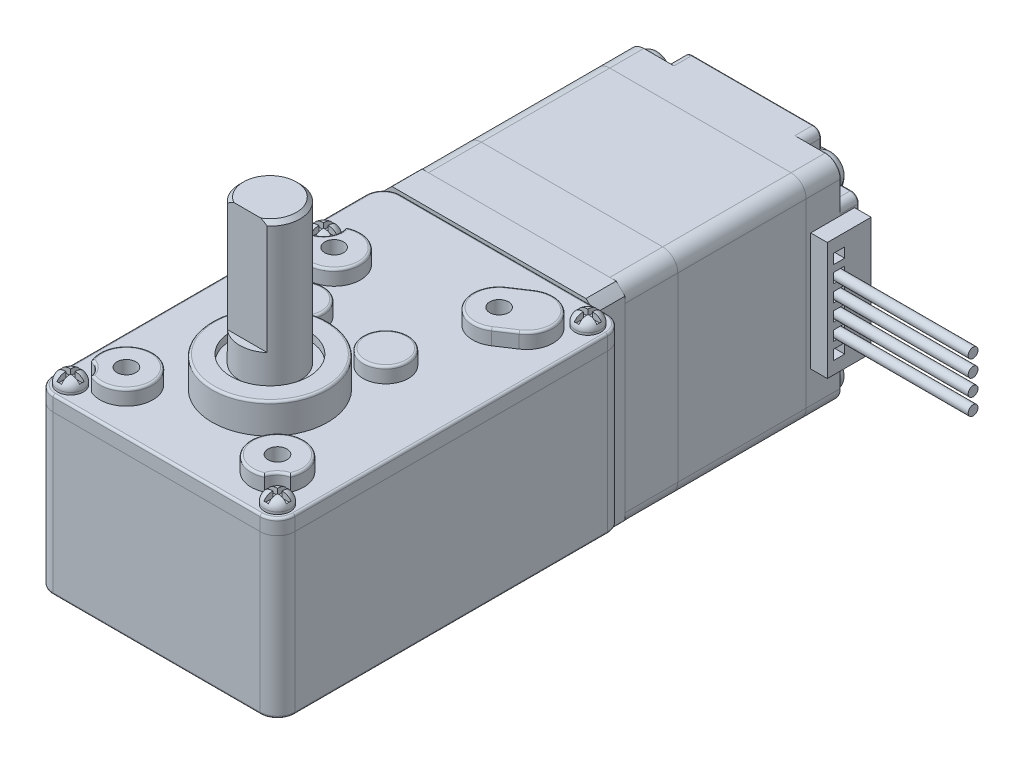
SolidWorks part; units mm, degrees
ref_plane "前视基准面" through (0, 0, 0) normal (0, 0, 1) x (1, 0, 0)
ref_plane "上视基准面" through (0, 0, 0) normal (0, 1, 0) x (1, 0, 0)
ref_plane "右视基准面" through (0, 0, 0) normal (1, 0, 0) x (0, 0, -1)
sketch "草图1" plane through (0, 0, 0) normal (0, 0, 1) x (1, 0, 0)
  line L0 (-49.7438, 0) -> (46.5346, 0) construction
  line L1 (0, 31.2288) -> (0, -36.9067) construction
  line L2 (-14, -14) -> (14, -14)
  line L3 (-14, 14) -> (-14, -14)
  line L4 (-14, 14) -> (14, 14)
  line L5 (14, 14) -> (14, -14)
  line L6 (-49.7438, -14) -> (46.5346, -14) construction
  line L7 (-14, 31.2288) -> (-14, -36.9067) construction
  line L8 (14, 31.2288) -> (14, -36.9067) construction
  line L9 (-49.7438, 14) -> (46.5346, 14) construction
  dimension "D1" = 14
  dimension "D2" = 14
extrude "拉伸1" add sketch "草图1" along normal blind 7
fillet "圆角5" radius 2 4 edges at (-14, -14, 3.5) (-14, 14, 3.5) (14, -14, 3.5) (14, 14, 3.5)
sketch "草图5" plane through (0, 0, 0) normal (0, 0, -1) x (-1, 0, 0)
  circle A0 centre (0, 0) radius 3
  dimension "D1" = 6
extrude "切除-拉伸1" cut sketch "草图5" against normal blind 2
sketch "草图6" plane through (0, 0, 0) normal (0, 0, -1) x (-1, 0, 0)
  line L0 (-24.7944, 0) -> (26.333, 0) construction
  line L1 (0, 25.3862) -> (0, -26.5696) construction
  line L2 (-11, 25.3862) -> (-11, -26.5696) construction
  line L3 (-24.7944, -11) -> (26.333, -11) construction
  line L4 (-14, -12) -> (-14, 12) construction
  line L5 (-14, -9) -> (-14, -14)
  line L6 (-9, -11) -> (-9, -14)
  line L7 (-14, -9) -> (-11, -9)
  line L8 (-14, -14) -> (-9, -14)
  line L9 (-9, 14) -> (-14, 14)
  line L10 (-9, 25.3862) -> (-9, -26.5696) construction
  line L11 (-14, 25.3862) -> (-14, -26.5696) construction
  line L12 (-24.7944, -9) -> (26.333, -9) construction
  line L13 (-24.7944, -14) -> (26.333, -14) construction
  line L14 (-11, 9) -> (-14, 9)
  line L15 (-9, 14) -> (-9, 11)
  line L16 (-14, 14) -> (-14, 9)
  line L17 (14, 9) -> (14, 14)
  line L18 (9, 11) -> (9, 14)
  line L19 (14, 9) -> (11, 9)
  line L20 (14, 14) -> (9, 14)
  line L21 (9, -14) -> (14, -14)
  line L22 (11, -9) -> (14, -9)
  line L23 (9, -14) -> (9, -11)
  line L24 (14, -14) -> (14, -9)
  arc A0 (-9, -11) -> (-11, -9) centre (-11, -11) ccw
  arc A1 (-11, 9) -> (-9, 11) centre (-11, 11) ccw
  arc A2 (9, 11) -> (11, 9) centre (11, 11) ccw
  arc A3 (11, -9) -> (9, -11) centre (11, -11) ccw
  point P21 (-9, 25.3862)
  point P22 (-9, -26.5696)
  point P23 (9, 25.3862)
  point P24 (9, -26.5696)
  point P25 (-24.7944, -9)
  point P26 (26.333, -9)
  point P27 (-24.7944, 9)
  point P28 (26.333, 9)
  point P29 (-14, 25.3862)
  point P30 (-14, -26.5696)
  point P31 (-24.7944, -14)
  point P32 (26.333, -14)
  point P33 (14, 25.3862)
  point P34 (14, -26.5696)
  point P35 (-24.7944, 14)
  point P36 (26.333, 14)
  dimension "D3" = 9
  dimension "D1" = 11
  dimension "D2" = 4
  dimension "D5" = 14
extrude "切除-拉伸2" cut sketch "草图6" against normal blind 2.5
sketch "草图40" plane through (0, 0, 7) normal (0, 0, 1) x (1, 0, 0)
  line L0 (-12, 14) -> (12, 14)
  line L1 (-12, -14) -> (12, -14) construction
  line L2 (14, 12) -> (14, -12)
  line L3 (12, 14) -> (-12, 14) construction
  line L4 (12, -14) -> (-12, -14)
  line L6 (-14, -12) -> (-14, 12)
  arc A0 (14, 12) -> (12, 14) centre (12, 12) ccw construction
  arc A1 (14, 12) -> (12, 14) centre (12, 12) ccw
  arc A2 (12, -14) -> (14, -12) centre (12, -12) ccw
  arc A3 (-14, -12) -> (-12, -14) centre (-12, -12) ccw
  arc A5 (-12, 14) -> (-14, 12) centre (-12, 12) ccw
extrude "凸台-拉伸28" add sketch "草图40" along normal blind 17 separate body
sketch "草图12" plane through (0, 0, 24) normal (0, 0, 1) x (1, 0, 0)
  line L0 (14, 12) -> (14, -12)
  line L1 (12, -14) -> (-12, -14)
  line L2 (-14, -12) -> (-14, 12)
  line L3 (-12, 14) -> (12, 14)
  arc A0 (-12, 14) -> (-14, 12) centre (-12, 12) ccw
  arc A1 (14, 12) -> (12, 14) centre (12, 12) ccw
  arc A2 (12, -14) -> (14, -12) centre (12, -12) ccw
  arc A3 (-14, -12) -> (-12, -14) centre (-12, -12) ccw
  arc A4 (14, 12) -> (12, 14) centre (12, 12) ccw construction
extrude "凸台-拉伸9" add sketch "草图12" along normal blind 7 separate body
sketch "草图14" plane through (0, 0, 31) normal (0, 0, -1) x (-1, 0, 0)
  line L0 (0, 14.44) -> (0, -16.3076) construction
  line L1 (14.7902, 0) -> (-17.5581, 0) construction
  line L4 (12.8452, 14) -> (-12.8452, 14)
  line L5 (-14, 12.8452) -> (-14, -12.8452)
  line L6 (12.8452, -14) -> (-12.8452, -14)
  line L7 (14, 12.8452) -> (14, -12.8452)
  line L9 (14.7902, 14) -> (-17.5581, 14) construction
  line L10 (-14, 14.44) -> (-14, -16.3076) construction
  line L11 (14.7902, -14) -> (-17.5581, -14) construction
  line L12 (14, 14.44) -> (14, -16.3076) construction
  arc A0 (-14, -12.8452) -> (-12.8452, -14) centre (0, 0) ccw
  arc A1 (-12.8452, 14) -> (-14, 12.8452) centre (0, 0) ccw
  arc A2 (12.8452, -14) -> (14, -12.8452) centre (0, 0) ccw
  arc A3 (14, 12.8452) -> (12.8452, 14) centre (0, 0) ccw
  dimension "D1" = 38
  dimension "D2" = 14
  dimension "D3" = 14
extrude "凸台-拉伸12" add sketch "草图14" against normal blind 4 separate body
sketch "草图27" plane through (0, 0, 2.5) normal (0, 0, 1) x (1, 0, 0)
  line L0 (0, 15.5683) -> (0, -17.9848) construction
  line L1 (16.498, 0) -> (-17.986, 0) construction
  line L2 (-11.5, 15.5683) -> (-11.5, -17.9848) construction
  line L3 (16.498, 11.5) -> (-17.986, 11.5) construction
  line L4 (11.5, 15.5683) -> (11.5, -17.9848) construction
  line L5 (16.498, -11.5) -> (-17.986, -11.5) construction
  circle A0 centre (11.5, 11.5) radius 2.1
  circle A1 centre (11.5, -11.5) radius 2.1
  circle A2 centre (-11.5, -11.5) radius 2.1
  circle A3 centre (-11.5, 11.5) radius 2.1
  dimension "D1" = 4.2
  dimension "D3" = 11.5
  dimension "D4" = 11.5
  dimension "D2" = 4
extrude "凸台-拉伸22" add sketch "草图27" against normal blind 1.5 separate body
sketch "草图28" plane through (0, 0, 1) normal (0, 0, -1) x (-1, 0, 0)
  line L0 (-11.5, 15.0277) -> (-11.5, 7.0398) construction
  line L1 (-14.8299, 11.5) -> (-7.2996, 11.5) construction
  line L2 (-11.8, 13) -> (-11.8, 11.8)
  line L3 (-13, 11.2) -> (-11.8, 11.2)
  line L4 (-11.2, 13) -> (-11.2, 11.8)
  line L5 (-13, 11.8) -> (-11.8, 11.8)
  line L6 (-11.8, 10) -> (-11.2, 10)
  line L7 (-13, 11.8) -> (-13, 11.2)
  line L8 (-11.8, 13) -> (-11.2, 13)
  line L9 (-10, 11.8) -> (-10, 11.2)
  line L10 (-11.2, 11.8) -> (-10, 11.8)
  line L11 (-14.8299, 11.2) -> (-7.2996, 11.2) construction
  line L12 (-14.8299, 11.8) -> (-7.2996, 11.8) construction
  line L13 (-14.8299, 13) -> (-7.2996, 13) construction
  line L14 (-14.8299, 10) -> (-7.2996, 10) construction
  line L15 (-10, 15.0277) -> (-10, 7.0398) construction
  line L16 (-11.2, 15.0277) -> (-11.2, 7.0398) construction
  line L17 (-11.8, 15.0277) -> (-11.8, 7.0398) construction
  line L18 (-13, 15.0277) -> (-13, 7.0398) construction
  line L19 (-11.8, 11.2) -> (-11.8, 10)
  line L20 (-11.2, 11.2) -> (-11.2, 10)
  line L21 (-11.2, 11.2) -> (-10, 11.2)
  line L22 (13, 11.8) -> (11.8, 11.8)
  line L23 (11.2, 13) -> (11.2, 11.8)
  line L24 (13, 11.2) -> (11.8, 11.2)
  line L25 (11.8, 13) -> (11.8, 11.8)
  line L26 (10, 11.8) -> (10, 11.2)
  line L27 (11.8, 13) -> (11.2, 13)
  line L28 (13, 11.8) -> (13, 11.2)
  line L29 (11.8, 10) -> (11.2, 10)
  line L30 (11.8, 11.2) -> (11.8, 10)
  line L31 (11.2, 11.8) -> (10, 11.8)
  line L32 (11.2, 11.2) -> (10, 11.2)
  line L33 (11.2, 11.2) -> (11.2, 10)
  line L34 (15.0277, 11.5) -> (7.0398, 11.5) construction
  line L35 (11.8, -13) -> (11.8, -11.8)
  line L36 (13, -11.2) -> (11.8, -11.2)
  line L37 (11.2, -13) -> (11.2, -11.8)
  line L38 (13, -11.8) -> (11.8, -11.8)
  line L39 (11.8, -10) -> (11.2, -10)
  line L40 (13, -11.8) -> (13, -11.2)
  line L41 (11.8, -13) -> (11.2, -13)
  line L42 (10, -11.8) -> (10, -11.2)
  line L43 (11.2, -11.8) -> (10, -11.8)
  line L44 (11.8, -11.2) -> (11.8, -10)
  line L45 (11.2, -11.2) -> (11.2, -10)
  line L46 (11.2, -11.2) -> (10, -11.2)
  line L47 (11.5, -15.0277) -> (11.5, -7.0398) construction
  line L48 (-13, -11.8) -> (-11.8, -11.8)
  line L49 (-11.2, -13) -> (-11.2, -11.8)
  line L50 (-13, -11.2) -> (-11.8, -11.2)
  line L51 (-11.8, -13) -> (-11.8, -11.8)
  line L52 (-10, -11.8) -> (-10, -11.2)
  line L53 (-11.8, -13) -> (-11.2, -13)
  line L54 (-13, -11.8) -> (-13, -11.2)
  line L55 (-11.8, -10) -> (-11.2, -10)
  line L56 (-11.8, -11.2) -> (-11.8, -10)
  line L57 (-11.2, -11.8) -> (-10, -11.8)
  line L58 (-11.2, -11.2) -> (-10, -11.2)
  line L59 (-11.2, -11.2) -> (-11.2, -10)
  line L60 (-15.0277, -11.5) -> (-7.0398, -11.5) construction
  point P6 (-3.8186, 14.7)
  point P7 (3.7709, 14.7)
  point P8 (-0.3, 18.4312)
  point P9 (-0.3, 11.6161)
  point P10 (-3.8186, 15.3)
  point P11 (3.7709, 15.3)
  point P12 (0.3, 18.4312)
  point P13 (0.3, 11.6161)
  point P14 (-3.8186, 13.5)
  point P15 (3.7709, 13.5)
  point P16 (-1.5, 18.4312)
  point P17 (-1.5, 11.6161)
  point P18 (-3.8186, 16.5)
  point P19 (3.7709, 16.5)
  point P20 (1.5, 18.4312)
  point P21 (1.5, 11.6161)
  dimension "D1" = 0.3
  dimension "D2" = 0.3
  dimension "D3" = 1.5
  dimension "D4" = 1.5
extrude "切除-拉伸6" cut sketch "草图28" against normal blind 1
fillet "圆角2" radius 1 1 edges at (13.6, 11.5, 1) tangent propagation no
fillet "圆角7" radius 1 1 edges at (-9.4, 11.5, 1)
fillet "圆角8" radius 1 1 edges at (13.6, -11.5, 1)
fillet "圆角9" radius 1 1 edges at (-9.4, -11.5, 1)
sketch "草图37" plane through (14, 0, 0) normal (-1, 0, 0) x (0, -1, 0)
  line L0 (0, -4.5496) -> (0, 16.2158) construction
  line L1 (-7.8, 0.6) -> (7.8, 0.6)
  line L3 (7.8, 0.6) -> (7.8, 6.4)
  line L4 (-7.8, 0.6) -> (-7.8, 6.4)
  line L5 (-7.8, 6.4) -> (7.8, 6.4)
  line L6 (0.45, 5.6) -> (1.75, 5.6)
  line L7 (-6.15, 5.6) -> (-4.85, 5.6)
  line L8 (7.8, -4.5496) -> (7.8, 16.2158) construction
  line L9 (-7.8, -4.5496) -> (-7.8, 16.2158) construction
  line L10 (-6.15, 4.1) -> (-4.85, 4.1)
  line L11 (1.1, -4.5496) -> (1.1, 16.2158) construction
  line L12 (-1.1, -4.5496) -> (-1.1, 16.2158) construction
  line L13 (3.3, -4.5496) -> (3.3, 16.2158) construction
  line L14 (5.5, -4.5496) -> (5.5, 16.2158) construction
  line L15 (-3.3, -4.5496) -> (-3.3, 16.2158) construction
  line L16 (-5.5, -4.5496) -> (-5.5, 16.2158) construction
  line L17 (-8.9281, 4.9) -> (9.1208, 4.9) construction
  line L18 (6.15, 4.1) -> (6.15, 5.6)
  line L19 (3.95, 4.1) -> (3.95, 5.6)
  line L20 (1.75, 4.1) -> (1.75, 5.6)
  line L21 (-0.45, 4.1) -> (-0.45, 5.6)
  line L22 (-2.65, 4.1) -> (-2.65, 5.6)
  line L23 (-4.85, 4.1) -> (-4.85, 5.6)
  line L24 (4.85, 4.1) -> (4.85, 5.6)
  line L25 (2.65, 4.1) -> (2.65, 5.6)
  line L26 (0.45, 4.1) -> (0.45, 5.6)
  line L27 (-1.75, 4.1) -> (-1.75, 5.6)
  line L28 (-3.95, 4.1) -> (-3.95, 5.6)
  line L29 (-6.15, 4.1) -> (-6.15, 5.6)
  line L30 (4.85, 5.6) -> (6.15, 5.6)
  line L31 (6.15, -4.5496) -> (6.15, 16.2158) construction
  line L32 (4.85, -4.5496) -> (4.85, 16.2158) construction
  line L33 (2.65, 5.6) -> (3.95, 5.6)
  line L34 (3.95, -4.5496) -> (3.95, 16.2158) construction
  line L35 (2.65, -4.5496) -> (2.65, 16.2158) construction
  line L36 (1.75, -4.5496) -> (1.75, 16.2158) construction
  line L37 (0.45, -4.5496) -> (0.45, 16.2158) construction
  line L38 (-1.75, 5.6) -> (-0.45, 5.6)
  line L39 (-0.45, -4.5496) -> (-0.45, 16.2158) construction
  line L40 (-1.75, -4.5496) -> (-1.75, 16.2158) construction
  line L41 (-3.95, 5.6) -> (-2.65, 5.6)
  line L42 (-2.65, -4.5496) -> (-2.65, 16.2158) construction
  line L43 (-3.95, -4.5496) -> (-3.95, 16.2158) construction
  line L44 (4.85, 4.1) -> (6.15, 4.1)
  line L45 (-4.85, -4.5496) -> (-4.85, 16.2158) construction
  line L46 (-6.15, -4.5496) -> (-6.15, 16.2158) construction
  line L47 (2.65, 4.1) -> (3.95, 4.1)
  line L48 (0.45, 4.1) -> (1.75, 4.1)
  line L49 (-1.75, 4.1) -> (-0.45, 4.1)
  line L50 (-3.95, 4.1) -> (-2.65, 4.1)
  line L51 (9, 0) -> (-9, 0) construction
  dimension "D5" = 5.8
  dimension "D6" = 0.8
  dimension "D4" = 3.5
  dimension "D13" = 4.3
  dimension "D16" = 0.6
  dimension "D2" = 7.8
  dimension "D3" = 7.8
  dimension "D7" = 1.1
  dimension "D8" = 1.1
  dimension "D9" = 2.2
  dimension "D10" = 2.2
  dimension "D11" = 2.2
  dimension "D12" = 2.2
  dimension "D14" = 0.65
  dimension "D15" = 0.65
extrude "凸台-拉伸25" add sketch "草图37" against normal blind 2.2 separate body
sketch "草图39" plane through (14, 0, 0) normal (-1, 0, 0) x (0, -1, 0)
  line L0 (0, -0.7021) -> (0, 10.1229) construction
  line L1 (1.1, 8.6125) -> (1.1, -1.5582) construction
  line L2 (-1.1, 8.6125) -> (-1.1, -1.3457) construction
  line L3 (-6.2419, 4.9) -> (5.6594, 4.9) construction
  line L4 (9, 0) -> (-9, 0) construction
  circle A0 centre (-3.3, 4.9) radius 0.65
  circle A1 centre (3.3, 4.9) radius 0.65
  circle A2 centre (-1.1, 4.9) radius 0.65
  circle A3 centre (1.1, 4.9) radius 0.65
  dimension "D4" = 2.2
  dimension "D6" = 1.3
  dimension "D1" = 1.1
  dimension "D2" = 1.1
  dimension "D3" = 4.9
  dimension "D5" = 2.2
extrude "凸台-拉伸27" add sketch "草图39" against normal blind 20 separate body contours A3 | A2 | A1 | A0
fillet "圆角10" radius 0.2 16 edges at (9, 12.5, 0) (9.5858, 9.5858, 0) (12.5, -9, 0) (9.5858, -9.5858, 0) (-9, -12.5, 0) (-12.5, 9, 0) (-9.5858, 9.5858, 0) (12.5, 9, 0) (14, 0, 0) (9, -12.5, 0) (0, -14, 0) (-9.5858, -9.5858, 0) (-12.5, -9, 0) (-14, 0, 0) (-9, 12.5, 0) (0, 14, 0)
fillet "圆角11" radius 1 16 edges at (13.9414, -8.9414, 0.0586) (8.9414, -13.9414, 0.0586) (-8.9414, -13.9414, 0.0586) (-13.9414, -8.9414, 0.0586) (13.9414, 8.9414, 0.0586) (8.9414, 13.9414, 0.0586) (-8.9414, 13.9414, 0.0586) (-13.9414, 8.9414, 0.0586) (14, -9, 1.35) (9, -14, 1.35) (-9, -14, 1.35) (-14, -9, 1.35) (14, 9, 1.35) (9, 14, 1.35) (-9, 14, 1.35) (-14, 9, 1.35)
sketch "草图59" plane through (0, 0, 2) normal (0, 0, -1) x (-1, 0, 0)
  circle A0 centre (0, 0) radius 2.5
  dimension "D1" = 5
extrude "凸台-拉伸40" add sketch "草图59" along normal blind 12
chamfer "倒角5" distance 0.5 angle 45 1 edges at (-2.5, 0, -10)
sketch "草图60" plane through (0, 0, 35) normal (0, 0, 1) x (1, 0, 0)
  line L0 (0, 22.1975) -> (0, -31.9546) construction
  line L1 (2, 25.8564) -> (2, -52.4446) construction
  line L2 (-14, 11.7) -> (-14, -9.3)
  line L3 (18, 11.7) -> (18, -9.3)
  line L4 (-23.5401, 0) -> (63.7862, 0) construction
  line L5 (-14, 11.7) -> (18, 11.7)
  line L6 (-14, -9.3) -> (18, -9.3)
  line L8 (18, 25.8564) -> (18, -52.4446) construction
  line L9 (-14, 11.7) -> (12.5612, 11.7) construction
  line L10 (-14, 25.8564) -> (-14, -52.4446) construction
  line L11 (-14, -9.3) -> (12.5612, -9.3) construction
  dimension "D1" = 2
  dimension "D4" = 11.7
  dimension "D5" = 21
  dimension "D2" = 16
  dimension "D3" = 16
extrude "凸台-拉伸41" add sketch "草图60" along normal blind 46 separate body
sketch "草图61" plane through (0, 11.7, 0) normal (0, 1, 0) x (1, 0, 0)
  line L0 (-14, -81) -> (-14, -35) construction
  line L1 (-12.8452, -35) -> (12.8452, -35) construction
  line L2 (-11.7, -35) -> (-14, -35)
  line L3 (-14, -35) -> (-14, -37.3)
  arc A0 (-11.7, -35) -> (-14, -37.3) centre (-11.7, -37.3) ccw
  dimension "D1" = 4.6
extrude "切除-拉伸16" cut sketch "草图61" against normal through all
fillet "圆角12" radius 2.3 3 edges at (18, 1.2, 35) (-14, 1.2, 81) (18, 1.2, 81)
sketch "草图62" plane through (0, -9.3, 0) normal (0, -1, 0) x (1, 0, 0)
  line L0 (2, 96.4087) -> (2, 38.1045) construction
  line L2 (-21.4932, 66) -> (47.5131, 66) construction
  line L3 (-11.7, 81) -> (15.7, 81) construction
  circle A0 centre (2, 66) radius 5
  circle A1 centre (-4.2633, 55.6272) radius 3
  circle A2 centre (6.9654, 55.6272) radius 3
  circle A3 centre (9.8, 43.4529) radius 3
  dimension "D3" = 10
  dimension "D4" = 6
  dimension "D5" = 6
  dimension "D6" = 6
  dimension "D1" = 2
  dimension "D2" = 15
  dimension "D7" = 22.5471
  dimension "D8" = 7.8
  dimension "D9" = 11.5
  dimension "D10" = 12.5
  dimension "D11" = 11.2287
  dimension "D12" = 6.2633
extrude "凸台-拉伸48" add sketch "草图62" along normal blind 2.2
fillet "圆角35" radius 0.3 4 edges at (-4.2633, -11.5, 52.6272) (9.8, -11.5, 40.4529) (6.9654, -11.5, 52.6272) (2, -11.5, 61)
fillet "圆角17" radius 0.3 2 edges at (2, -9.3, 81) (18, -9.3, 58) tangent propagation no
fillet "圆角18" radius 0.3 5 edges at (2, -9.3, 35) (16.8571, -9.3, 35.3123) (-13.6877, -9.3, 79.8571) (-14, -9.3, 58) (-13.3263, -9.3, 35.6737)
fillet "圆角19" radius 0.3 1 edges at (17.3263, -9.3, 80.3263)
sketch "草图63" plane through (0, 11.7, 0) normal (0, 1, 0) x (1, 0, 0)
  line L0 (-14, -37.3) -> (-14, -78.7)
  line L1 (-11.7, -35) -> (15.7, -35)
  line L2 (-12.8452, -35) -> (12.8452, -35) construction
  line L3 (18, -37.3) -> (18, -78.7)
  line L4 (-11.7, -81) -> (15.7, -81)
  arc A0 (-11.7, -35) -> (-14, -37.3) centre (-11.7, -37.3) ccw construction
  arc A1 (-11.7, -35) -> (-14, -37.3) centre (-11.7, -37.3) ccw
  arc A2 (18, -37.3) -> (15.7, -35) centre (15.7, -37.3) ccw
  arc A3 (15.7, -81) -> (18, -78.7) centre (15.7, -78.7) ccw
  arc A4 (-14, -78.7) -> (-11.7, -81) centre (-11.7, -78.7) ccw
extrude "凸台-拉伸43" add sketch "草图63" along normal blind 2 separate body
fillet "圆角32" radius 0.3 8 edges at (-13.3263, 13.7, 80.3263) (-14, 13.7, 58) (-13.3263, 13.7, 35.6737) (2, 13.7, 35) (17.3263, 13.7, 35.6737) (18, 13.7, 58) (17.3263, 13.7, 80.3263) (2, 13.7, 81)
sketch "草图64" plane through (0, 13.7, 0) normal (0, 1, 0) x (1, 0, 0)
  line L0 (2, -44.3474) -> (2, -100.0875) construction
  line L1 (-19.4865, -66) -> (28.5615, -66) construction
  line L2 (15.7, -81) -> (-11.7, -81) construction
  line L3 (-19.4865, -75) -> (28.5615, -75) construction
  line L4 (-19.4865, -42) -> (28.5615, -42) construction
  line L5 (-8, -44.3474) -> (-8, -100.0875) construction
  line L6 (12, -44.3474) -> (12, -100.0875) construction
  line L7 (-19.4865, -47.5) -> (28.5615, -47.5) construction
  line L8 (7.8713, -40.5322) -> (10.0713, -39.0794)
  line L9 (11.7287, -46.3735) -> (13.9287, -44.9206)
  line L10 (-19.4865, -78.7) -> (28.5615, -78.7) construction
  line L11 (-19.4865, -37.3) -> (28.5615, -37.3) construction
  line L12 (-11.7, -44.3474) -> (-11.7, -100.0875) construction
  line L13 (15.7, -44.3474) -> (15.7, -100.0875) construction
  line L14 (-16.6239, -45.2) -> (-5.6461, -45.2) construction
  circle A0 centre (2, -66) radius 7.65
  arc A1 (-11.5, -47.4913) -> (-9.5568, -44.3653) centre (-8, -47.5) ccw
  arc A2 (13.9287, -44.9206) -> (10.0713, -39.0794) centre (12, -42) ccw
  arc A3 (15.1813, -76.4593) -> (13.4593, -78.1813) centre (12, -75) ccw
  arc A4 (-9.4593, -78.1813) -> (-11.1813, -76.4593) centre (-8, -75) ccw
  circle A5 centre (-4.2633, -55.6272) radius 3
  circle A6 centre (6.9654, -55.6272) radius 3
  arc A7 (7.8713, -40.5322) -> (11.7287, -46.3735) centre (9.8, -43.4529) ccw
  arc A8 (-9.4593, -78.1813) -> (-11.1813, -76.4593) centre (-11.7, -78.7) ccw
  arc A9 (15.1813, -76.4593) -> (13.4593, -78.1813) centre (15.7, -78.7) ccw
  arc A10 (-11.5, -47.4913) -> (-9.5568, -44.3653) centre (-11.7, -45.2) ccw
  dimension "D8" = 15.3
  dimension "D9" = 7
  dimension "D14" = 4.6
  dimension "D16" = 4.6
  dimension "D1" = 2
  dimension "D2" = 15
  dimension "D15" = 33.5
  dimension "D3" = 9
  dimension "D4" = 33
  dimension "D5" = 10
  dimension "D6" = 10
  dimension "D7" = 27.5
  dimension "D10" = 12.7
  dimension "D11" = 41.4
  dimension "D12" = 13.7
  dimension "D13" = 13.7
extrude "凸台-拉伸44" add sketch "草图64" along normal blind 2 contours A1 | A6 | A5 | A3 | A2 L8 A7 L9 | A4 A8 region at (-7.7483, 13.7, 47.6564) region at (11.9433, 13.7, 74.9433) region at (-4.2633, 13.7, 55.6272) region at (6.9654, 13.7, 55.6272)
extrude "凸台-拉伸45" add sketch "草图64<3>" along normal blind 4 contours A0 region at (2, 13.7, 66)
sketch "草图64<3>" plane through (0, 13.7, 0) normal (0, 1, 0) x (1, 0, 0) same geometry as "草图64"
sketch "草图65" plane through (0, 13.7, 0) normal (0, 1, 0) x (1, 0, 0)
  line L0 (-16.0608, -78.7) -> (22.6677, -78.7) construction
  line L1 (-20.86, -37.6) -> (31.0384, -37.6) construction
  line L2 (2, 1.5269) -> (2, -98.0287) construction
  line L3 (-11.7, 1.5269) -> (-11.7, -98.0287) construction
  line L4 (15.7, 1.5269) -> (15.7, -98.0287) construction
  line L5 (-20.86, -45.2) -> (-3.6091, -45.2) construction
  circle A0 centre (-11.7, -45.2) radius 1.7
  circle A1 centre (-11.7, -78.7) radius 1.7
  circle A2 centre (15.7, -78.7) radius 1.7
  circle A3 centre (15.7, -37.6) radius 1.7
  dimension "D4" = 3.4
  dimension "D1" = 41.1
  dimension "D5" = 33.5
  dimension "D2" = 13.7
  dimension "D3" = 13.7
extrude "凸台-拉伸46" add sketch "草图65" along normal blind 1.5
sketch "草图66" plane through (0, 15.2, 0) normal (0, 1, 0) x (1, 0, 0)
  line L0 (-15.4597, -45.2) -> (19.4532, -45.2) construction
  line L1 (-15.863, -78.7) -> (19.4532, -78.7) construction
  line L2 (-11.7, -46.7218) -> (-11.7, -96.0378) construction
  line L3 (15.7, -46.1456) -> (15.7, -95.5769) construction
  line L4 (-13.2, -45.5) -> (-12, -45.5)
  line L5 (-13.2, -79) -> (-12, -79)
  line L6 (-12, -43.7) -> (-12, -44.9)
  line L7 (-13.2, -44.9) -> (-12, -44.9)
  line L8 (-13.2, -78.4) -> (-12, -78.4)
  line L9 (-11.4, -43.7) -> (-11.4, -44.9)
  line L10 (12.852, -37.6) -> (17.2, -37.6) construction
  line L11 (14.2, -37.9) -> (15.4, -37.9)
  line L12 (-13.2, -44.9) -> (-13.2, -45.5)
  line L13 (-12, -46.7) -> (-11.4, -46.7)
  line L14 (-12, -80.2) -> (-11.4, -80.2)
  line L15 (15.4, -36.1) -> (15.4, -37.3)
  line L16 (-10.2, -44.9) -> (-10.2, -45.5)
  line L17 (-12, -43.7) -> (-11.4, -43.7)
  line L18 (-12, -77.2) -> (-11.4, -77.2)
  line L19 (14.2, -37.3) -> (15.4, -37.3)
  line L20 (15.4, -80.2) -> (16, -80.2)
  line L21 (16, -36.1) -> (16, -37.3)
  line L22 (14.2, -37.3) -> (14.2, -37.9)
  line L23 (15.4, -39.1) -> (16, -39.1)
  line L24 (17.2, -37.3) -> (17.2, -37.9)
  line L25 (-15.863, -80.2) -> (19.4532, -80.2) construction
  line L26 (-15.863, -79) -> (19.4532, -79) construction
  line L27 (-15.863, -78.4) -> (19.4532, -78.4) construction
  line L28 (-15.863, -77.2) -> (19.4532, -77.2) construction
  line L29 (-10.2, -78.4) -> (-10.2, -79)
  line L30 (-10.2, -46.7218) -> (-10.2, -96.0378) construction
  line L31 (-11.4, -46.7218) -> (-11.4, -96.0378) construction
  line L32 (-12, -46.7218) -> (-12, -96.0378) construction
  line L33 (-13.2, -46.7218) -> (-13.2, -96.0378) construction
  line L34 (15.4, -77.2) -> (16, -77.2)
  line L35 (14.2, -78.4) -> (15.4, -78.4)
  line L36 (14.2, -79) -> (15.4, -79)
  line L37 (-13.2, -78.4) -> (-13.2, -79)
  line L38 (-12, -77.2) -> (-12, -78.4)
  line L39 (-11.4, -77.2) -> (-11.4, -78.4)
  line L40 (-11.4, -78.4) -> (-10.2, -78.4)
  line L41 (-11.4, -79) -> (-11.4, -80.2)
  line L42 (-12, -79) -> (-12, -80.2)
  line L43 (-11.4, -79) -> (-10.2, -79)
  line L44 (17.2, -78.4) -> (17.2, -79)
  line L45 (14.2, -78.4) -> (14.2, -79)
  line L46 (16, -77.2) -> (16, -78.4)
  line L47 (15.4, -77.2) -> (15.4, -78.4)
  line L48 (16, -78.4) -> (17.2, -78.4)
  line L49 (15.4, -79) -> (15.4, -80.2)
  line L50 (16, -79) -> (16, -80.2)
  line L51 (16, -79) -> (17.2, -79)
  line L52 (15.4, -36.1) -> (16, -36.1)
  line L53 (-15.4597, -43.7) -> (19.4532, -43.7) construction
  line L54 (-15.4597, -44.9) -> (19.4532, -44.9) construction
  line L55 (-15.4597, -45.5) -> (19.4532, -45.5) construction
  line L56 (-15.4597, -46.7) -> (19.4532, -46.7) construction
  line L57 (16, -37.9) -> (16, -39.1)
  line L58 (17.2, -46.1456) -> (17.2, -95.5769) construction
  line L59 (15.4, -46.1456) -> (15.4, -95.5769) construction
  line L60 (14.2, -46.1456) -> (14.2, -95.5769) construction
  line L61 (12.852, -36.1) -> (19.4532, -36.1) construction
  line L62 (16, -46.1456) -> (16, -95.5769) construction
  line L63 (12.852, -37.3) -> (19.4532, -37.3) construction
  line L64 (-11.4, -45.5) -> (-10.2, -45.5)
  line L65 (-11.4, -44.9) -> (-10.2, -44.9)
  line L66 (-12, -45.5) -> (-12, -46.7)
  line L67 (-11.4, -45.5) -> (-11.4, -46.7)
  line L68 (12.852, -37.6) -> (19.4532, -37.6) construction
  line L69 (12.852, -37.9) -> (19.4532, -37.9) construction
  line L70 (12.852, -39.1) -> (19.4532, -39.1) construction
  line L71 (15.4, -37.9) -> (15.4, -39.1)
  line L72 (16, -37.3) -> (17.2, -37.3)
  line L73 (16, -37.9) -> (17.2, -37.9)
  point P25 (15.4, -46.1456)
  point P26 (15.4, -95.5769)
  point P27 (16, -46.1456)
  point P28 (16, -95.5769)
  point P35 (14.2, -46.1456)
  point P36 (14.2, -95.5769)
  point P43 (17.2, -46.1456)
  point P44 (17.2, -95.5769)
  dimension "D1" = 0.3
  dimension "D2" = 0.3
  dimension "D3" = 0.3
  dimension "D4" = 0.3
  dimension "D5" = 1.5
  dimension "D6" = 1.5
  dimension "D7" = 1.5
  dimension "D8" = 1.5
extrude "切除-拉伸17" cut sketch "草图66" against normal blind 0.8
fillet "圆角33" radius 1.2 4 edges at (15.7, 15.2, 80.4) (15.7, 15.2, 39.3) (-11.7, 15.2, 46.9) (-11.7, 15.2, 80.4)
fillet "圆角34" radius 0.3 13 edges at (8.9713, 15.7, 39.8058) (14.9206, 15.7, 40.0713) (12.8287, 15.7, 45.647) (-4.2633, 15.7, 58.6272) (-5.0275, 15.7, 49.3478) (6.8794, 15.7, 45.3816) (6.9654, 15.7, 58.6272) (2, 17.7, 73.65) (14.0737, 15.7, 77.0737) (9.5251, 15.7, 72.5251) (-10.0737, 15.7, 77.0737) (-5.5251, 15.7, 72.5251) (-9.7466, 15.7, 46.4142)
sketch "草图67" plane through (0, 17.7, 0) normal (0, 1, 0) x (1, 0, 0)
  circle A0 centre (2, -66) radius 5.15
  dimension "D1" = 10.3
extrude "切除-拉伸18" cut sketch "草图67" against normal blind 1
sketch "草图68" plane through (0, 16.7, 0) normal (0, 1, 0) x (1, 0, 0)
  circle A0 centre (2, -66) radius 4
  dimension "D1" = 8
extrude "凸台-拉伸47" add sketch "草图68" along normal blind 19
sketch "草图69" plane through (0, 35.7, 0) normal (0, 1, 0) x (1, 0, 0)
  line L0 (-0.6458, -69) -> (4.6458, -69)
  arc A0 (-0.6458, -69) -> (4.6458, -69) centre (2, -66) ccw
  circle A1 centre (2, -66) radius 4 construction
  dimension "D1" = 7
extrude "切除-拉伸19" cut sketch "草图69" against normal blind 15
chamfer "倒角6" distance 0.5 angle 45 1 edges at (2, 35.7, 62)
sketch "草图70" plane through (0, 15.7, 0) normal (0, 1, 0) x (1, 0, 0)
  line L0 (-17.4958, -47.5) -> (23.5527, -47.5) construction
  line L1 (-17.4958, -75) -> (20.2063, -75) construction
  line L2 (-8, -49.254) -> (-8, -97.8875) construction
  line L3 (12, -49.254) -> (12, -97.8875) construction
  line L4 (5.2593, -43.4529) -> (20.2063, -43.4529) construction
  line L5 (9.8, -61.4124) -> (9.8, -35.3) construction
  line L6 (15.7, -35.3) -> (-11.7, -35.3) construction
hole_wizard "M3 螺纹孔1" positions "3D草图1" profile "草图71" tap size "M3" standard "GB"
sketch3d "3D草图1"
  line L0 (-17.4958, 15.7, 47.5) -> (23.5527, 15.7, 47.5) construction
  line L1 (5.2593, 15.7, 43.4529) -> (20.2063, 15.7, 43.4529) construction
  line L2 (-17.4958, 15.7, 75) -> (20.2063, 15.7, 75) construction
  line L3 (-8, 15.7, 49.254) -> (-8, 15.7, 97.8875) construction
  line L4 (9.8, 15.7, 61.4124) -> (9.8, 15.7, 35.3) construction
  line L5 (12, 15.7, 49.254) -> (12, 15.7, 97.8875) construction
  point P0 (-8, 15.7, 47.5)
  point P4 (9.8, 15.7, 43.4529)
  point P8 (12, 15.7, 75)
  point P12 (-8, 15.7, 75)
sketch "草图71" plane through (-8, 15.7, 47.5) normal (1, 0, 0) x (0, 0, 1)
  line L0 (0, 0) -> (0, 8.2511)
  line L1 (0, 8.2511) -> (1.25, 7.5)
  line L2 (1.25, 7.5) -> (1.25, 0)
  line L5 (1.25, 0) -> (0, 0)
  line L10 (0, 8.2511) -> (-1.25, 7.5) construction
  line L11 (0, -6.35) -> (0, 107.95) construction
  dimension "螺纹孔钻头直径" = 2.5
  dimension "螺纹孔钻头深度" = 7.5
  dimension "导头角度" = 118
cosmetic thread "孔螺蚊线1" parameters "D1"=5, "D2"=3
cosmetic thread "孔螺蚊线2" parameters "D1"=5, "D2"=3
cosmetic thread "孔螺蚊线3" parameters "D1"=5, "D2"=3
cosmetic thread "孔螺蚊线4" parameters "D1"=5, "D2"=3
sketch "草图72" plane through (0, 0, -10) normal (0, 0, -1) x (-1, 0, 0)
  line L0 (-2, -1.5) -> (-2, 1.5)
  arc A0 (-2, 1.5) -> (-2, -1.5) centre (0, 0) ccw
  dimension "D1" = 5
  dimension "D2" = 4.5
extrude "切除-拉伸20" cut sketch "草图72" against normal blind 9
